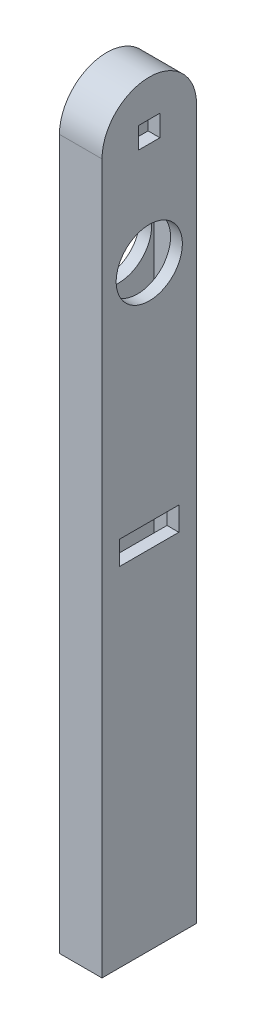
SolidWorks part; units mm, degrees
ref_plane "Front Plane" through (0, 0, 0) normal (0, 0, 1) x (1, 0, 0)
ref_plane "Top Plane" through (0, 0, 0) normal (0, 1, 0) x (1, 0, 0)
ref_plane "Right Plane" through (0, 0, 0) normal (1, 0, 0) x (0, 0, -1)
sketch "Sketch2" plane through (0, 0, 0) normal (1, 0, 0) x (0, 0, -1)
  line L0 (-20, 0) -> (20, 0) construction
  line L1 (-20, 48) -> (-20, -252)
  line L2 (20, 48) -> (20, -252)
  line L3 (0, 0) -> (0, 48) construction
  line L4 (20, 48) -> (-20, 48) construction
  line L5 (-4.5, 43.5) -> (4.5, 43.5)
  line L6 (-4.5, 43.5) -> (-4.5, 52.5)
  line L7 (-4.5, 52.5) -> (4.5, 52.5)
  line L8 (4.5, 43.5) -> (4.5, 52.5)
  line L9 (-4.5, 43.5) -> (4.5, 52.5) construction
  line L10 (-4.5, 52.5) -> (4.5, 43.5) construction
  line L11 (-20, -252) -> (20, -252) construction
  line L12 (0, 0) -> (0, -150) construction
  line L13 (15, 48) -> (15, -247)
  line L14 (-15, 48) -> (-15, -247)
  line L15 (-20, -252) -> (20, -252)
  line L16 (-15, -247) -> (15, -247)
  line L17 (-15, 48) -> (-15, -252) construction
  line L18 (15, 48) -> (15, -252) construction
  line L19 (0, -150) -> (0, -239) construction
  line L20 (-20, -239) -> (20, -239) construction
  circle A0 centre (0, 0) radius 14
  arc A1 (-20, 48) -> (20, 48) centre (0, 48) cw
  circle A2 centre (0, -150) radius 10
  arc A6 (-15, 48) -> (15, 48) centre (0, 48) cw
  arc A7 (-20, -252) -> (20, -252) centre (0, -252) ccw construction
  arc A8 (-15, -252) -> (15, -252) centre (0, -252) ccw construction
  dimension "D1" = 28
  dimension "D7" = 20
  dimension "D2" = 40
  dimension "D3" = 48
  dimension "D4" = 9
  dimension "D5" = 300
  dimension "D6" = 150
  dimension "D8" = 5
  dimension "D10" = 8
  dimension "D9" = 5
sketch "Sketch3" plane through (0, 0, 0) normal (0, 0, 1) x (1, 0, 0)
  line L0 (-145.1347, 0) -> (145.1347, 0) construction
  line L1 (0, -164.4063) -> (0, 164.4063) construction
  line L2 (0, 48) -> (0, -252) construction
  point P3 (-4, 0)
  point P7 (-9, 0)
  point P12 (0, 0)
  dimension "D1" = 18
  dimension "D2" = 5
extrude "Boss-Extrude1" add sketch "Sketch2" along normal up to vertex (-4 mm away) from vertex contours L1 L15 L2 A1 L14 A6 L13 | A6 L14 L13 L8 L5 L6 L7 A0 A2 | A2 region at (0, 64.7751, 0) region at (0, -99.8624, 0) region at (0, -150, 0) up to point (-4, 0, 0) starting at point (-9, 0, 0)
extrude "Boss-Extrude2" add sketch "Sketch2<6>" along normal up to surface from vertex contours L1 L15 L2 A1 L14 A6 L13 region at (0, 64.7751, 0) up to plane "Right Plane" starting at point (-4, 0, 0)
sketch "Sketch2<6>" plane through (0, 0, 0) normal (1, 0, 0) x (0, 0, -1) same geometry as "Sketch2"
mirror "Mirror1" about plane through (0, 0, 0) normal (1, 0, 0) of bodies 103
sketch "Sketch4" plane through (0, 0, 0) normal (1, 0, 0) x (0, 0, -1)
  line L0 (0, 0) -> (0, -150) construction
  line L1 (-12.5, -105) -> (12.5, -105)
  line L2 (-12.5, -105) -> (-12.5, -95)
  line L3 (-12.5, -95) -> (12.5, -95)
  line L4 (12.5, -105) -> (12.5, -95)
  line L5 (-12.5, -105) -> (12.5, -95) construction
  line L6 (-12.5, -95) -> (12.5, -105) construction
  point P0 (0, -100)
  dimension "D1" = 10
  dimension "D2" = 45
  dimension "D3" = 25
extrude "Cut-Extrude1" cut sketch "Sketch4" against normal up to next from surface starting at face at (9, -97, 0)
equation "\"D8@Sketch2\"=\"D9@Sketch2\""
